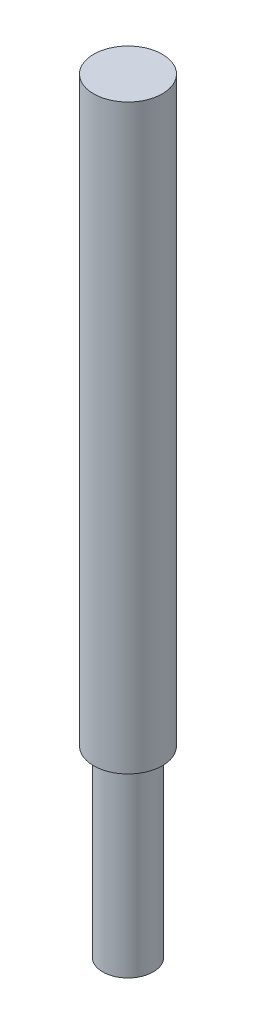
SolidWorks part; units mm, degrees
material "6061 Alloy"
ref_plane "Front Plane" through (0, 0, 0) normal (0, 0, 1) x (1, 0, 0)
ref_plane "Top Plane" through (0, 0, 0) normal (0, 1, 0) x (1, 0, 0)
ref_plane "Right Plane" through (0, 0, 0) normal (1, 0, 0) x (0, 0, -1)
sketch "Sketch1" plane through (0, 0, 0) normal (0, 1, 0) x (1, 0, 0)
  circle A0 centre (0, 0) radius 2.3813
  dimension "D1" = 4.7625
extrude "Boss-Extrude1" add sketch "Sketch1" along normal blind 40.3733
sketch "Sketch2" plane through (0, 0, 0) normal (0, -1, 0) x (1, 0, 0)
  circle A0 centre (0, 0) radius 1.7526
  dimension "D1" = 3.5052
extrude "Boss-Extrude2" add sketch "Sketch2" along normal blind 12.7
